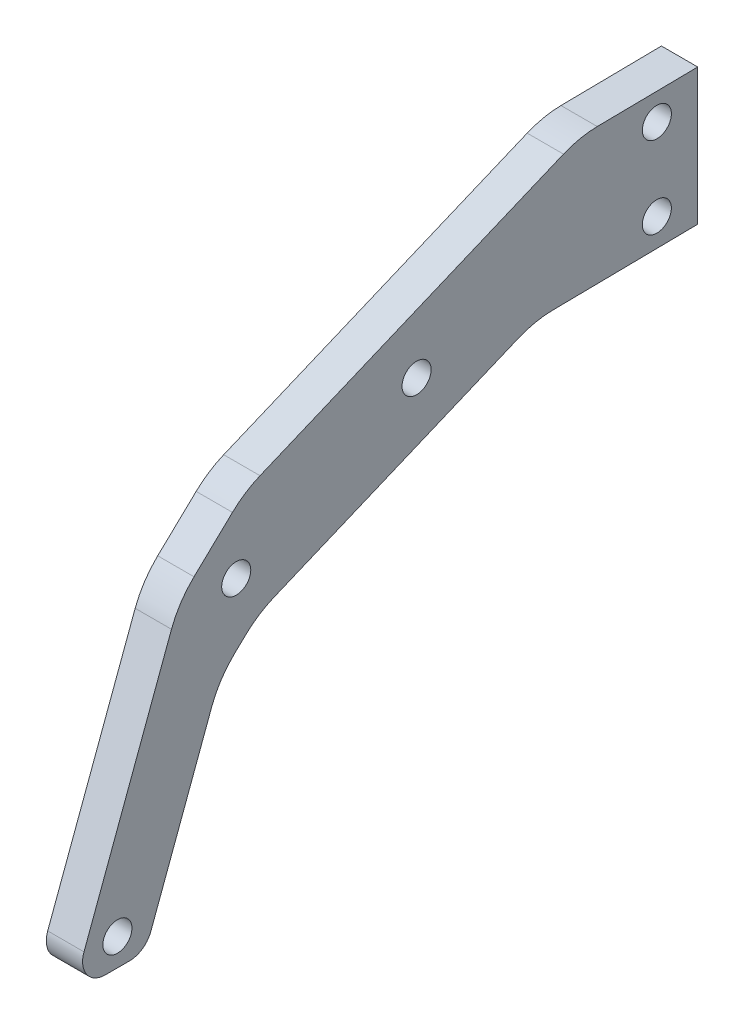
SolidWorks part; units mm, degrees
ref_plane "Front Plane" through (0, 0, 0) normal (0, 0, 1) x (1, 0, 0)
ref_plane "Top Plane" through (0, 0, 0) normal (0, 1, 0) x (1, 0, 0)
ref_plane "Right Plane" through (0, 0, 0) normal (1, 0, 0) x (0, 0, -1)
sketch "Sketch1" plane through (0, 0, 0) normal (1, 0, 0) x (0, 0, -1)
  line L0 (3.5946, 0) -> (6.2613, 0)
  line L1 (8.605, 1.63) -> (16.1383, 21.9252)
  line L2 (16.1383, 21.9252) -> (20.4267, 26.0029)
  line L3 (20.4267, 26.0029) -> (50.9139, 38.7396)
  line L4 (50.9139, 38.7396) -> (68.8447, 38.9779)
  line L6 (11.6904, 31.495) -> (18.9373, 38.3858)
  line L7 (18.9373, 38.3858) -> (55.8459, 53.8051)
  line L10 (68.8447, 38.9779) -> (68.8447, 53.9779)
  line L13 (1.2509, 3.37) -> (11.6904, 31.495)
  line L14 (55.8459, 53.8051) -> (68.8447, 53.9779)
  line L15 (35.5671, 45.3332) -> (40.1929, 34.2606) construction
  line L16 (14.5715, 34.2345) -> (21.4623, 26.9876) construction
  circle A0 centre (64.3447, 50.9779) radius 1.6
  circle A1 centre (4.928, 3) radius 1.6
  circle A2 centre (18.0169, 30.6111) radius 1.6
  arc A3 (6.2613, 0) -> (8.605, 1.63) centre (6.2613, 2.5) ccw
  arc A4 (3.5946, 0) -> (1.2509, 3.37) centre (3.5946, 2.5) cw
  circle A5 centre (37.88, 39.7969) radius 1.6
  circle A6 centre (64.3403, 41.9779) radius 1.6
  point P11 (37.88, 39.7969)
  point P19 (18.0169, 30.6111)
  point P21 (4.928, 0)
  point P22 (18.0169, 30.6111)
  point P27 (8, 0)
  point P30 (0, 0)
  point P34 (68.8447, 46.4779)
  dimension "D2" = 3.2
  dimension "D6" = 2.5
  dimension "D1" = 8
  dimension "D3" = 4.5
  dimension "D4" = 15
  dimension "D5" = 3
  dimension "D7" = 10
  dimension "D8" = 7.5
  dimension "D9" = 12
  dimension "D10" = 40
  dimension "D11" = 10
  dimension "D12" = 30
  dimension "D13" = 13
  dimension "D14" = 9
  dimension "D15" = 4.5
extrude "Boss-Extrude1" add sketch "Sketch1" along normal blind 4 contours A0 | A5 | A2 | A1 | A6 | L13 L6 L7 L14 L10 L4 L3 L2 L1 A3 L0 A4 region at (0, 50.9779, -64.3447) region at (0, 3, -4.928) region at (0, 30.6111, -18.0169) region at (0, 39.7969, -37.88) region at (0, 41.9779, -64.3403)
fillet "Fillet1" radius 10 6 edges at (2, 53.8051, -55.8459) (2, 31.495, -11.6904) (2, 38.3858, -18.9373) (2, 21.9252, -16.1383) (2, 26.0029, -20.4267) (2, 38.7396, -50.9139)
